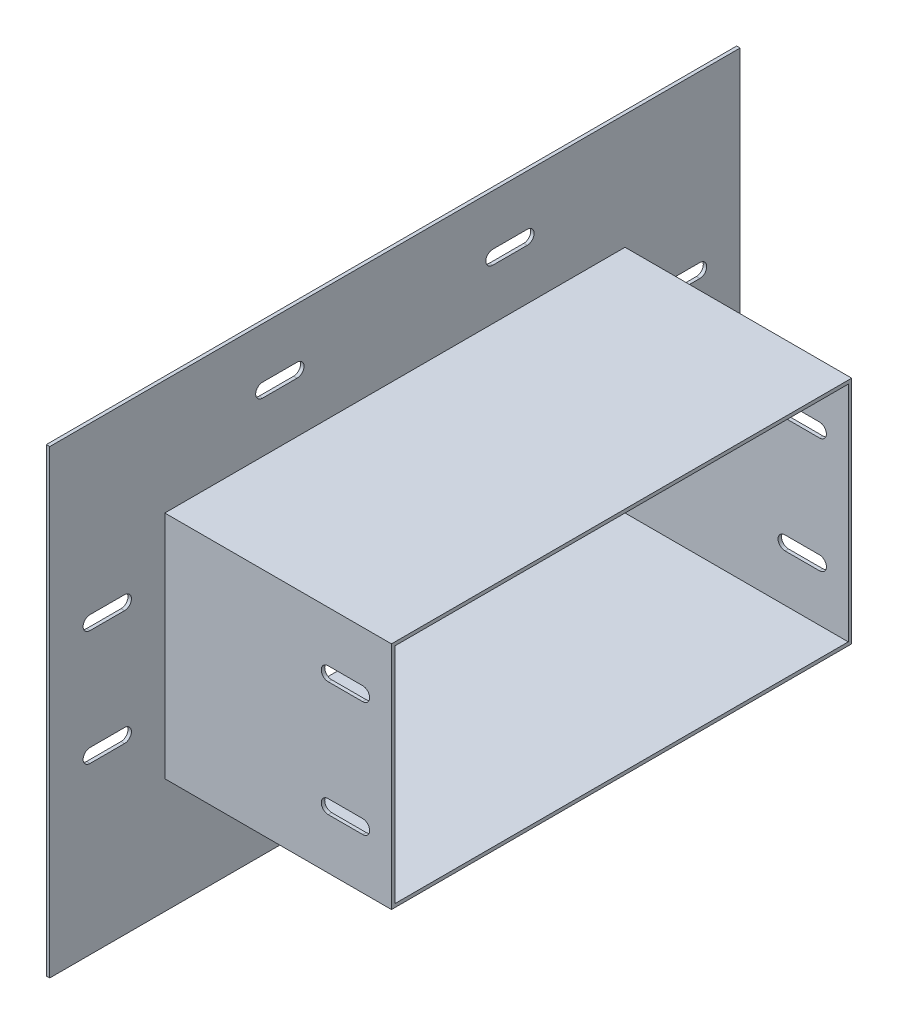
SolidWorks part; units mm, degrees
material "Plain Carbon Steel"
ref_plane "Front Plane" through (0, 0, 0) normal (0, 0, 1) x (1, 0, 0)
ref_plane "Top Plane" through (0, 0, 0) normal (0, 1, 0) x (1, 0, 0)
ref_plane "Right Plane" through (0, 0, 0) normal (1, 0, 0) x (0, 0, -1)
sketch "Sketch1" plane through (0, 0, 0) normal (1, 0, 0) x (0, -1, 0)
  line L2 (50, 100) -> (50, -100)
  line L3 (-50, 100) -> (-50, -100)
  line L5 (50, -100) -> (-50, -100)
  line L11 (50, 100) -> (-50, 100)
  point P1 (50, 0)
  point P3 (0, -100)
  dimension "Width" = 200
extrude "Extrude-Thin1" add sketch "Sketch1" along normal blind 100 thin thin type one direction reverse wall 1.5
sketch "Sketch2" plane through (0, 0, 0) normal (1, 0, 0) x (0, 0, -1)
  line L0 (-100, 50) -> (-100, -50)
  line L2 (100, 50) -> (100, -50)
  line L3 (-100, 50) -> (100, 50)
  line L4 (-150, 100) -> (-150, -100)
  line L5 (150, -100) -> (-150, -100)
  line L6 (150, 100) -> (150, -100)
  line L7 (-150, 100) -> (150, 100)
  line L8 (100, -50) -> (-100, -50)
  dimension "D1" = 50
extrude "Boss-Extrude2" add sketch "Sketch2" along normal blind 1.5
sketch "Sketch3" plane through (0, 0, 0) normal (0, 0, 1) x (1, 0, 0)
  line L0 (72.5, 25) -> (87.5, 25) construction
  line L1 (72.5, 28) -> (87.5, 28)
  line L2 (72.5, 22) -> (87.5, 22)
  line L3 (72.5, -25) -> (87.5, -25) construction
  line L4 (72.5, -22) -> (87.5, -22)
  line L5 (72.5, -28) -> (87.5, -28)
  line L6 (60, 0) -> (100, 0) construction
  line L8 (100, 50) -> (1.5, 50) construction
  line L9 (80, -50) -> (80, 0) construction
  line L10 (100, 50) -> (100, -50) construction
  line L11 (80, 0) -> (80, 50) construction
  arc A0 (72.5, 28) -> (72.5, 22) centre (72.5, 25) ccw
  arc A1 (87.5, 22) -> (87.5, 28) centre (87.5, 25) ccw
  arc A2 (72.5, -22) -> (72.5, -28) centre (72.5, -25) ccw
  arc A3 (87.5, -28) -> (87.5, -22) centre (87.5, -25) ccw
  point P2 (80, 25)
  point P8 (80, -25)
  dimension "D1" = 3
  dimension "D2" = 15
  dimension "D3" = 40
extrude "Cut-Extrude1" cut sketch "Sketch3" against normal through all and the other way through all
sketch "Sketch4" plane through (1.5, 0, 0) normal (1, 0, 0) x (0, 0, -1)
  line L0 (-150, 0) -> (-100, 0) construction
  line L1 (0, -100) -> (0, -50) construction
  line L2 (-150, 100) -> (-150, -100) construction
  line L3 (-150, -100) -> (150, -100) construction
  line L4 (-100, 50) -> (-100, -50) construction
  line L5 (-125, 0) -> (-125, 50) construction
  line L6 (-125, 0) -> (-125, -50) construction
  line L7 (-57.5, 75) -> (-42.5, 75) construction
  line L8 (-57.5, 78) -> (-42.5, 78)
  line L9 (-57.5, 72) -> (-42.5, 72)
  line L10 (-132.5, -25) -> (-117.5, -25) construction
  line L11 (-132.5, -22) -> (-117.5, -22)
  line L12 (-132.5, -28) -> (-117.5, -28)
  line L13 (150, 0) -> (100, 0) construction
  line L14 (150, -100) -> (150, 100) construction
  line L15 (-132.5, 25) -> (-117.5, 25) construction
  line L16 (-132.5, 28) -> (-117.5, 28)
  line L17 (-132.5, 22) -> (-117.5, 22)
  line L18 (-57.5, -75) -> (-42.5, -75) construction
  line L19 (-57.5, -72) -> (-42.5, -72)
  line L20 (-57.5, -78) -> (-42.5, -78)
  line L21 (100, -50) -> (100, 50) construction
  line L22 (0, 50) -> (0, 100) construction
  line L23 (100, 50) -> (-100, 50) construction
  line L24 (117.5, 25) -> (132.5, 25) construction
  line L25 (117.5, 28) -> (132.5, 28)
  line L26 (117.5, 22) -> (132.5, 22)
  line L27 (42.5, -75) -> (57.5, -75) construction
  line L28 (42.5, -72) -> (57.5, -72)
  line L29 (42.5, -78) -> (57.5, -78)
  line L30 (150, 100) -> (-150, 100) construction
  line L31 (-100, -50) -> (100, -50) construction
  line L33 (42.5, 75) -> (57.5, 75) construction
  line L34 (42.5, 78) -> (57.5, 78)
  line L35 (42.5, 72) -> (57.5, 72)
  line L36 (117.5, -25) -> (132.5, -25) construction
  line L37 (117.5, -22) -> (132.5, -22)
  line L38 (117.5, -28) -> (132.5, -28)
  line L39 (0, 75) -> (-100, 75) construction
  line L40 (0, 75) -> (100, 75) construction
  arc A0 (-57.5, 78) -> (-57.5, 72) centre (-57.5, 75) ccw
  arc A1 (-42.5, 72) -> (-42.5, 78) centre (-42.5, 75) ccw
  arc A2 (-132.5, -22) -> (-132.5, -28) centre (-132.5, -25) ccw
  arc A3 (-117.5, -28) -> (-117.5, -22) centre (-117.5, -25) ccw
  arc A4 (-132.5, 28) -> (-132.5, 22) centre (-132.5, 25) ccw
  arc A5 (-117.5, 22) -> (-117.5, 28) centre (-117.5, 25) ccw
  arc A6 (-57.5, -72) -> (-57.5, -78) centre (-57.5, -75) ccw
  arc A7 (-42.5, -78) -> (-42.5, -72) centre (-42.5, -75) ccw
  arc A8 (117.5, 28) -> (117.5, 22) centre (117.5, 25) ccw
  arc A9 (132.5, 22) -> (132.5, 28) centre (132.5, 25) ccw
  arc A10 (42.5, -72) -> (42.5, -78) centre (42.5, -75) ccw
  arc A11 (57.5, -78) -> (57.5, -72) centre (57.5, -75) ccw
  arc A12 (42.5, 78) -> (42.5, 72) centre (42.5, 75) ccw
  arc A13 (57.5, 72) -> (57.5, 78) centre (57.5, 75) ccw
  arc A14 (117.5, -22) -> (117.5, -28) centre (117.5, -25) ccw
  arc A15 (132.5, -28) -> (132.5, -22) centre (132.5, -25) ccw
  point P15 (-50, 75)
  point P21 (-125, -25)
  point P30 (125, 0)
  point P32 (-125, 25)
  point P38 (-50, -75)
  point P51 (125, 25)
  point P57 (50, -75)
  point P70 (50, 75)
  point P76 (125, -25)
  point P84 (0, -75)
  dimension "D1" = 3
  dimension "D2" = 15
extrude "Cut-Extrude2" cut sketch "Sketch4" against normal through all
sketch "Sketch5" plane through (100, 0, 0) normal (1, 0, 0) x (0, -1, 0)
  point P1 (0, 0)
  point P10 (0, 0)
other "CPoint1" parameters "Diameter"=10, "StubLength"=100
ref_axis "Axis1" through (110, 0, 0) along (-1, 0, 0)
other "RPoint1"
equation "\"D1@Sketch2\" = \"Height@Sketch1\" / 2"
equation "\"Length@Extrude-Thin1\"=\"Height@Sketch1\""
equation "\"Thickness@Boss-Extrude2\"=\"Thickness@Extrude-Thin1\""
